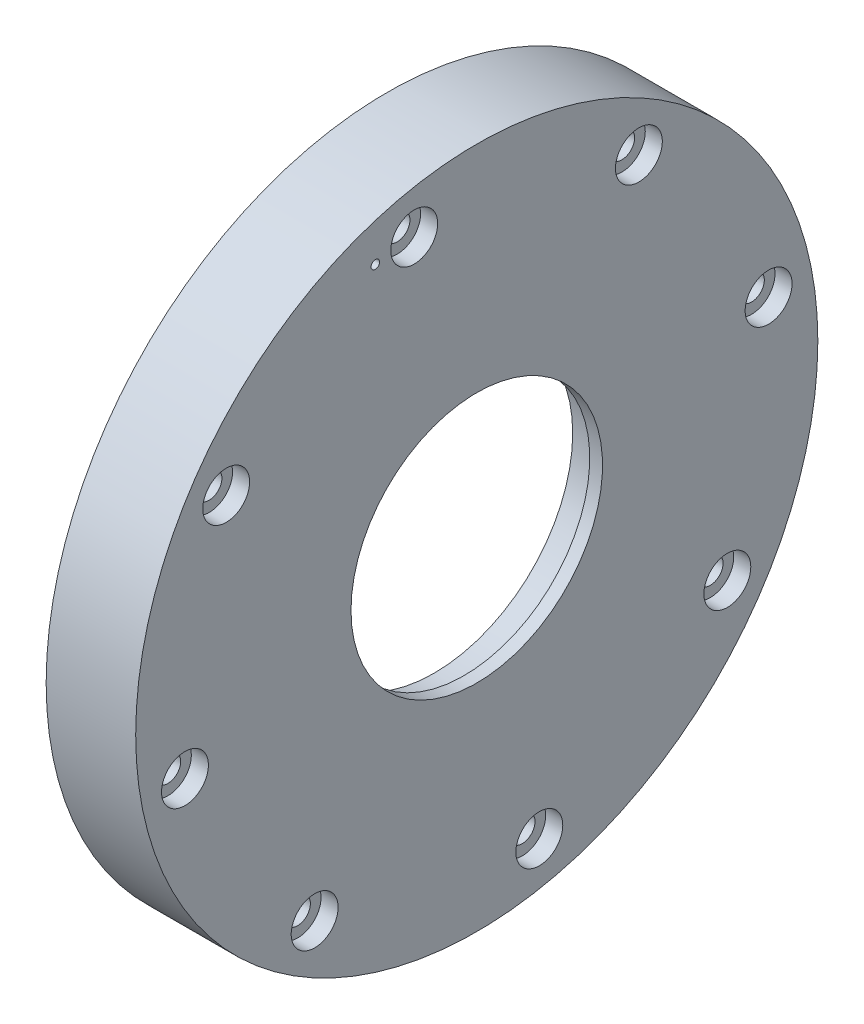
SolidWorks part; units mm, degrees
ref_plane "Front Plane" through (0, 0, 0) normal (0, 0, 1) x (1, 0, 0)
ref_plane "Top Plane" through (0, 0, 0) normal (0, 1, 0) x (1, 0, 0)
ref_plane "Right Plane" through (0, 0, 0) normal (1, 0, 0) x (0, 0, -1)
sketch "Sketch2" plane through (0, 0, 0) normal (0, 0, 1) x (1, 0, 0)
  line L0 (0, 0) -> (80.4799, 0) construction
  line L1 (0, 80) -> (0, 52.5)
  line L2 (0, 52.5) -> (11, 52.5)
  line L3 (11, 52.5) -> (11, 32.5)
  line L4 (11, 32.5) -> (18, 32.5)
  line L5 (18, 32.5) -> (18, 29.5)
  line L6 (18, 29.5) -> (21, 29.5)
  line L7 (21, 29.5) -> (21, 80)
  line L8 (21, 80) -> (0, 80)
  dimension "D1" = 80
  dimension "D2" = 32.5
  dimension "D3" = 52.5
  dimension "D4" = 18
  dimension "D5" = 3
  dimension "D6" = 7
  dimension "D7" = 3
revolve "Revolve1" add sketch "Sketch2" angle 360 about L0
sketch "Sketch3" plane through (0, 0, 0) normal (-1, 0, 0) x (0, 0, 1)
  circle A0 centre (0, 0) radius 60 construction
  circle A1 centre (0, 60) radius 2.51
  circle A2 centre (12.0779, 58.7718) radius 2.51
  circle A3 centre (23.6614, 55.1375) radius 2.51
  circle A4 centre (34.2761, 49.2458) radius 2.51
  circle A5 centre (43.4876, 41.338) radius 2.51
  circle A6 centre (50.9187, 31.7378) radius 2.51
  circle A7 centre (56.2651, 20.8383) radius 2.51
  circle A8 centre (59.3081, 9.0857) radius 2.51
  circle A9 centre (59.923, -3.039) radius 2.51
  circle A10 centre (58.0846, -15.0392) radius 2.51
  circle A11 centre (53.8683, -26.4236) radius 2.51
  circle A12 centre (47.4465, -36.7264) radius 2.51
  circle A13 centre (39.0823, -45.5255) radius 2.51
  circle A14 centre (29.1181, -52.4608) radius 2.51
  circle A15 centre (17.9618, -57.2484) radius 2.51
  circle A16 centre (6.0701, -59.6922) radius 2.51
  circle A17 centre (-6.0701, -59.6922) radius 2.51
  circle A18 centre (-17.9618, -57.2484) radius 2.51
  circle A19 centre (-29.1181, -52.4608) radius 2.51
  circle A20 centre (-39.0823, -45.5255) radius 2.51
  circle A21 centre (-47.4465, -36.7264) radius 2.51
  circle A22 centre (-53.8683, -26.4236) radius 2.51
  circle A23 centre (-58.0846, -15.0392) radius 2.51
  circle A24 centre (-59.923, -3.039) radius 2.51
  circle A25 centre (-59.3081, 9.0857) radius 2.51
  circle A26 centre (-56.2651, 20.8383) radius 2.51
  circle A27 centre (-50.9187, 31.7378) radius 2.51
  circle A28 centre (-43.4876, 41.338) radius 2.51
  circle A29 centre (-34.2761, 49.2458) radius 2.51
  circle A30 centre (-23.6614, 55.1375) radius 2.51
  circle A31 centre (-12.0779, 58.7718) radius 2.51
  point P67 (0, 0)
  dimension "D1" = 120
  dimension "D2" = 5.02
  dimension "D3" = 31
extrude "Cut-Extrude1" cut sketch "Sketch3" against normal blind 4
sketch "Sketch4" plane through (21, 0, 0) normal (1, 0, 0) x (0, 0, -1)
  circle A0 centre (-38.0255, -58.7712) radius 5.5
  circle A1 centre (-68.4457, -14.6694) radius 5.5
  circle A2 centre (-58.7712, 38.0255) radius 5.5
  circle A3 centre (-14.6694, 68.4457) radius 5.5
  circle A4 centre (38.0255, 58.7712) radius 5.5
  circle A5 centre (68.4457, 14.6694) radius 5.5
  circle A6 centre (58.7712, -38.0255) radius 5.5
  circle A7 centre (14.6694, -68.4457) radius 5.5
  point P16 (0, 0)
  dimension "D2" = 11
  dimension "D1" = 8
extrude "Cut-Extrude2" cut sketch "Sketch4" against normal blind 4
sketch "Sketch5" plane through (21, 0, 0) normal (1, 0, 0) x (0, 0, -1)
  circle A0 centre (-38.0255, -58.7712) radius 3
  circle A1 centre (-68.4457, -14.6694) radius 3
  circle A2 centre (-58.7712, 38.0255) radius 3
  circle A3 centre (-14.6694, 68.4457) radius 3
  circle A4 centre (38.0255, 58.7712) radius 3
  circle A5 centre (68.4457, 14.6694) radius 3
  circle A6 centre (58.7712, -38.0255) radius 3
  circle A7 centre (14.6694, -68.4457) radius 3
  point P16 (0, 0)
  dimension "D2" = 6
  dimension "D1" = 8
extrude "Cut-Extrude3" cut sketch "Sketch5" against normal through all
sketch "Sketch6" [suppressed] plane through (0, 0, 0) normal (-1, 0, 0) x (0, 0, 1)
  circle A0 centre (53.8756, 44.6925) radius 3
  circle A1 centre (69.6982, -6.4934) radius 3
  circle A2 centre (44.6925, -53.8756) radius 3
  circle A3 centre (-6.4934, -69.6982) radius 3
  circle A4 centre (-53.8756, -44.6925) radius 3
  circle A5 centre (-69.6982, 6.4934) radius 3
  circle A6 centre (-44.6925, 53.8756) radius 3
  circle A7 centre (6.4934, 69.6982) radius 3
  point P15 (0, 0)
  dimension "D2" = 6
  dimension "D1" = 8
extrude "Cut-Extrude4" [suppressed] cut sketch "Sketch6" against normal blind 11
sketch "Sketch7" [suppressed] plane through (21, 0, 0) normal (-1, 0, 0) x (0, 0, 1)
  circle A0 centre (53.8756, 44.6925) radius 3.3
  circle A1 centre (69.6982, -6.4934) radius 3.3
  circle A2 centre (44.6925, -53.8756) radius 3.3
  circle A3 centre (-6.4934, -69.6982) radius 3.3
  circle A4 centre (-53.8756, -44.6925) radius 3.3
  circle A5 centre (-69.6982, 6.4934) radius 3.3
  circle A6 centre (-44.6925, 53.8756) radius 3.3
  circle A7 centre (6.4934, 69.6982) radius 3.3
  point P15 (0, 0)
  dimension "D1" = 6.6
  dimension "D2" = 8
extrude "Cut-Extrude5" [suppressed] cut sketch "Sketch7" against normal through all
sketch "Sketch8" plane through (21, 0, 0) normal (1, 0, 0) x (0, 0, -1)
  circle A0 centre (-23.7966, 67.4351) radius 1
  dimension "D1" = 2
extrude "Cut-Extrude6" cut sketch "Sketch8" against normal blind 2
sketch "Sketch9" [suppressed] plane through (0, 0, 0) normal (-1, 0, 0) x (0, 0, 1)
  circle A0 centre (2.5177, -71.4663) radius 1
  dimension "D1" = 2
extrude "Cut-Extrude7" [suppressed] cut sketch "Sketch9" against normal blind 2
sketch "Sketch10" [suppressed] plane through (21, 0, 0) normal (1, 0, 0) x (0, 0, -1)
  line L0 (69.6982, 6.4934) -> (-44.6925, -53.8756) construction
  line L1 (23.4319, 37.2417) -> (0, 0) construction
  circle A0 centre (0, 0) radius 44 construction
  circle A1 centre (23.4319, 37.2417) radius 3.3
  circle A2 centre (20.5363, -38.9135) radius 3.3
  circle A3 centre (-43.9682, 1.6717) radius 3.3
  point P15 (0, 0)
  dimension "D1" = 6.6
  dimension "D2" = 88
  dimension "D3" = 30
  dimension "D4" = 3
extrude "Cut-Extrude8" [suppressed] cut sketch "Sketch10" against normal up to next
chamfer "Chamfer1" [suppressed] distance 0.5 angle 45
equation "\"R_ROLL\"= 5mm"
equation "\"D_SUN\"= 120mm"
equation "\"NUM_ROLL\"= 31"
equation "\"RHO\"= 1mm"
equation "\"D_SHAFT\"= 28mm"
equation "\"D_OUTPUT\"= 80mm"
equation "\"NUM_OUT\"= 8"
equation "\"R_OUT_ROLL\"= 5mm"
equation "\"D1@Sketch3\"=\"D_SUN\""
